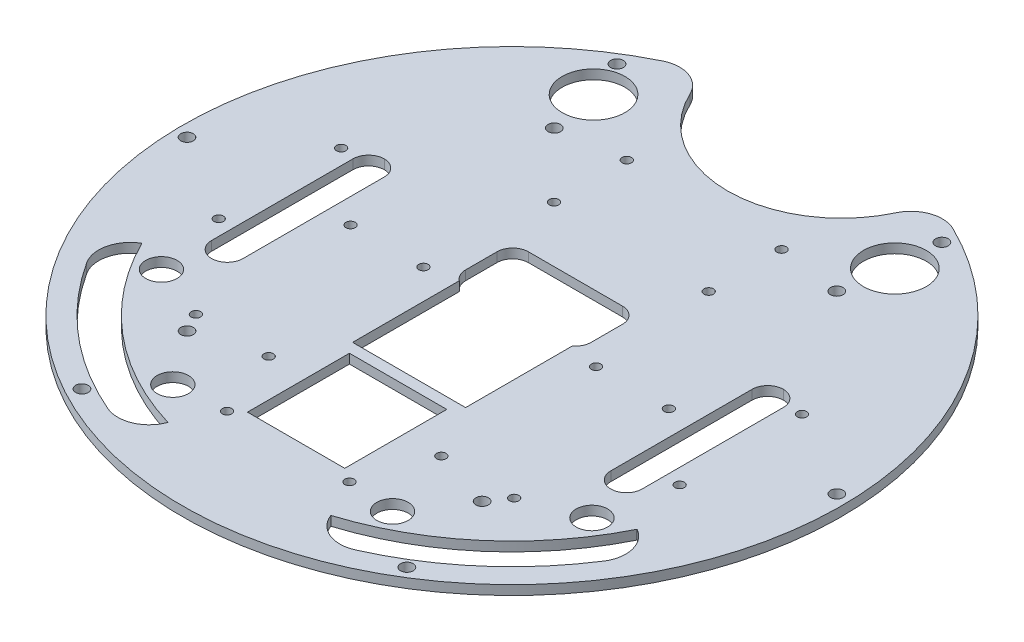
SolidWorks part; units mm, degrees
ref_plane "Alzado" through (0, 0, 0) normal (0, 0, 1) x (1, 0, 0)
ref_plane "Planta" through (0, 0, 0) normal (0, 1, 0) x (1, 0, 0)
ref_plane "Vista lateral" through (0, 0, 0) normal (1, 0, 0) x (0, 0, -1)
sketch "Croquis1" plane through (0, 0, 0) normal (0, 1, 0) x (1, 0, 0)
  circle A0 centre (0, 0) radius 105
  dimension "D1" = 210
extrude "Saliente-Extruir1" add sketch "Croquis1" along normal blind 3
sketch "Croquis2" plane through (0, 3, 0) normal (0, 1, 0) x (1, 0, 0)
  line L0 (-35.7167, 98.7386) -> (35.7167, 98.7386) construction
  line L1 (-29.7198, 68.7386) -> (25.5389, 68.7386) construction
  arc A0 (35.7167, 98.7386) -> (-35.7167, 98.7386) centre (0, 105) cw
  circle A2 centre (0, 0) radius 105 construction
  arc A3 (-35.7167, 98.7386) -> (35.7167, 98.7386) centre (0, 0) cw
  dimension "D1" = 30
extrude "Cortar-Extruir1" cut sketch "Croquis2" against normal up to surface (3 mm away) up to face at (0, 0, 105)
fillet "Redondeo1" radius 10 2 edges at (35.7167, 1.5, -98.7386) (-35.7167, 1.5, -98.7386)
sketch "Croquis3" plane through (0, 3, 0) normal (0, 1, 0) x (1, 0, 0)
  line L0 (0, 0) -> (0, -105) construction
  line L1 (-20, -105) -> (-20, -82) construction
  line L2 (-20, -82) -> (20, -82) construction
  line L3 (20, -82) -> (20, -105) construction
  line L4 (20, -105) -> (-20, -105) construction
  line L5 (-61.0141, 58.3205) -> (-85.2628, 72.3205)
  line L6 (-20, -82) -> (20, -82)
  line L7 (-20, -82) -> (-20, -110)
  line L8 (-20, -110) -> (20, -110)
  line L9 (20, -82) -> (20, -110)
  line L10 (-61.0141, 58.3205) -> (-81.0141, 23.6795)
  line L11 (-81.0141, 23.6795) -> (-105.2628, 37.6795)
  line L12 (-85.2628, 72.3205) -> (-105.2628, 37.6795)
  line L13 (81.0141, 23.6795) -> (105.2628, 37.6795)
  line L14 (81.0141, 23.6795) -> (61.0141, 58.3205)
  line L15 (61.0141, 58.3205) -> (85.2628, 72.3205)
  line L16 (105.2628, 37.6795) -> (85.2628, 72.3205)
  arc A0 (-46.2555, 94.2626) -> (46.2555, 94.2626) centre (0, 0) ccw construction
  point P23 (0, 0)
  point P29 (0, 0)
  point P44 (0, 0)
  dimension "D5" = 3
  dimension "D7" = 110
  dimension "D1" = 20
  dimension "D2" = 40
  dimension "D3" = 23
  dimension "D4" = 105
sketch "Croquis6" plane through (0, 3, 0) normal (0, 1, 0) x (1, 0, 0)
  line L0 (-14.5, -50) -> (-27.5, -50) construction
  line L1 (15.5, -50) -> (27.5, -50) construction
  line L2 (-27.5, -50) -> (-27.5, -0.7) construction
  line L3 (-27.5, -0.7) -> (-50.7, -0.7) construction
  line L4 (-27.5, -50) -> (-50.7, -50) construction
  line L5 (27.5, -50) -> (50.7, -50) construction
  line L6 (27.5, -50) -> (27.5, -0.7) construction
  line L7 (27.5, -0.7) -> (50.7, -0.7) construction
  line L8 (-24.6, 38) -> (24.7, 38) construction
  line L11 (-24.6, 38) -> (-24.6, 61.2) construction
  line L13 (24.7, 38) -> (24.7, 61.2) construction
  circle A0 centre (-50.7, -50) radius 1.5
  circle A1 centre (-27.5, -50) radius 1.5
  circle A2 centre (-50.7, -0.7) radius 1.5
  circle A3 centre (-27.5, -0.7) radius 1.5
  circle A4 centre (50.7, -0.7) radius 1.5
  circle A5 centre (50.7, -50) radius 1.5
  circle A6 centre (27.5, -50) radius 1.5
  circle A7 centre (27.5, -0.7) radius 1.5
  circle A8 centre (-24.6, 38) radius 1.5
  circle A9 centre (-24.6, 61.2) radius 1.5
  circle A10 centre (24.7, 38) radius 1.5
  circle A11 centre (24.7, 61.2) radius 1.5
  arc A12 (-46.2555, 94.2626) -> (46.2555, 94.2626) centre (0, 0) ccw construction
  arc A13 (-32.8037, 89.5468) -> (32.8037, 89.5468) centre (0, 105) ccw construction
  dimension "D1" = 3
  dimension "D2" = 3
  dimension "D3" = 3
  dimension "D4" = 3
  dimension "D5" = 3
  dimension "D6" = 3
  dimension "D7" = 3
  dimension "D8" = 3
  dimension "D9" = 3
  dimension "D10" = 3
  dimension "D11" = 3
  dimension "D12" = 3
  dimension "D17" = 23.2
  dimension "D18" = 23.2
  dimension "D19" = 23.2
  dimension "D20" = 23.2
  dimension "D23" = 23.2
  dimension "D24" = 23.2
  dimension "D13" = 27.5
  dimension "D14" = 27.5
  dimension "D15" = 49.3
  dimension "D16" = 49.3
  dimension "D21" = 67
  dimension "D22" = 49.3
  dimension "D25" = 24.6
  dimension "D26" = 50
  dimension "D27" = 50
extrude "Cortar-Extruir10" cut sketch "Croquis6" against normal through all
sketch "Croquis12" plane through (0, 3, 0) normal (0, 1, 0) x (1, 0, 0)
  line L0 (0, -110) -> (0, -89) construction
  line L1 (-19, -83.92) -> (-19, -103.2666) construction
  line L2 (-19, -83.92) -> (19, -83.92) construction
  line L3 (-19, -103.2666) -> (19, -103.2666) construction
  line L4 (-19, -49.2666) -> (-11.5, -49.2666) construction
  line L5 (-17, -17.8467) -> (-17, -34.8467) construction
  line L6 (19, -103.2666) -> (19, -83.92) construction
  line L7 (-19, -49.2666) -> (-19, -83.92) construction
  line L8 (-15.5, -36.2666) -> (15.5, -36.2666)
  line L9 (-15.5, -36.2666) -> (-15.5, -68.7666)
  line L10 (-15.5, -68.7666) -> (15.5, -68.7666)
  line L11 (15.5, -36.2666) -> (15.5, -68.7666)
  line L12 (0, 115.6879) -> (0, -186.0714) construction
  line L13 (-18, -32.7666) -> (18, -32.7666)
  line L14 (-18, -32.7666) -> (-18, -9.7666)
  line L15 (-18, -9.7666) -> (18, -9.7666)
  line L16 (18, -32.7666) -> (18, -9.7666)
  line L20 (-116.0467, -20.7666) -> (168.8024, -20.7666) construction
  line L24 (-17, -14.8467) -> (-17, -37.8467) construction
  arc A0 (-46.2555, 94.2626) -> (46.2555, 94.2626) centre (0, 0) ccw construction
  dimension "D6" = 15.1533
  dimension "D7" = 15.5
  dimension "D8" = 11
  dimension "D1" = 21
  dimension "D2" = 38
  dimension "D3" = 19.3467
  dimension "D4" = 7.5
  dimension "D5" = 13
  dimension "D16" = 31
  dimension "D17" = 32.5
  dimension "D19" = 3.5
  dimension "D20" = 23
  dimension "D21" = 36
  dimension "D22" = 18
extrude "Cortar-Extruir13" cut sketch "Croquis12" against normal through all
sketch "Croquis16" plane through (0, 3, 0) normal (0, 1, 0) x (1, 0, 0)
  line L0 (-22, -82) -> (22, -82) construction
  line L1 (0, -113.1983) -> (0, -59.2856) construction
  line L2 (-22, -82) -> (-22, -68.7666) construction
  line L3 (-22, -68.7666) -> (22, -68.7666) construction
  line L4 (22, -68.7666) -> (22, -82) construction
  line L5 (-134.3371, 0) -> (162.6467, 0) construction
  line L6 (-70.4267, 22) -> (-70.4267, -22) construction
  line L7 (-70.4267, 22) -> (-102.6694, 22) construction
  line L8 (-102.6694, 22) -> (-102.6694, -22) construction
  line L9 (-102.6694, -22) -> (-70.4267, -22) construction
  line L10 (-20, -82) -> (20, -82) construction
  circle A0 centre (-19, -71.7666) radius 1.5
  circle A1 centre (20, -71.7666) radius 1.5
  arc A2 (-46.2555, 94.2626) -> (46.2555, 94.2626) centre (0, 0) ccw construction
  circle A3 centre (-73.4267, 19) radius 1.5
  circle A4 centre (-73.4267, -20) radius 1.5
  circle A5 centre (73.4267, 19) radius 1.5
  circle A6 centre (73.4267, -20) radius 1.5
  dimension "D3" = 3
  dimension "D4" = 3
  dimension "D5" = 3
  dimension "D6" = 3
  dimension "D7" = 3
  dimension "D8" = 2
  dimension "D12" = 3
  dimension "D13" = 3
  dimension "D14" = 3
  dimension "D15" = 3
  dimension "D16" = 3
  dimension "D17" = 2
  dimension "D1" = 44
  dimension "D2" = 22
  dimension "D9" = 44
  dimension "D10" = 22
  dimension "D11" = 32.2427
extrude "Cortar-Extruir16" cut sketch "Croquis16" against normal through all
sketch "Croquis17" plane through (0, 3, 0) normal (0, 1, 0) x (1, 0, 0)
  line L0 (0, -118.708) -> (0, 122.5947) construction
  line L1 (-174.3343, -39) -> (185.7554, -39) construction
  line L2 (-20, -108.1665) -> (-20, -82) construction
  line L3 (20, -108.1665) -> (20, -82) construction
  line L4 (-31.4253, -100.1871) -> (-20.4928, -71.6203) construction
  line L5 (21.4314, -71.3181) -> (32.3639, -99.8878) construction
  line L6 (-20, -82) -> (-20, -110) construction
  line L7 (20, -82) -> (20, -110) construction
  arc A1 (-78.886, -39) -> (-25.3354, -84.2741) centre (0, 0) ccw
  arc A2 (-32.8037, 89.5468) -> (32.8037, 89.5468) centre (0, 105) ccw construction
  arc A4 (26.2784, -83.9848) -> (78.886, -39) centre (0, 0) ccw
  arc A5 (-46.2555, 94.2626) -> (46.2555, 94.2626) centre (0, 0) ccw construction
  circle A6 centre (-19, -71.7666) radius 1.5 construction
  circle A7 centre (20, -71.7666) radius 1.5 construction
  arc A8 (-46.2555, 94.2626) -> (46.2555, 94.2626) centre (0, 0) ccw construction
  dimension "D6" = 88
  dimension "D1" = 144
  dimension "D2" = 30.5873
  dimension "D3" = 20.942
  dimension "D4" = 30.59
  dimension "D5" = 20.94
extrude "Cortar-Extruir-Lámina2" cut sketch "Croquis17" against normal blind 10 thin thin type one direction wall 10
sketch "Croquis18" plane through (0, 3, 0) normal (0, 1, 0) x (1, 0, 0)
  line L1 (0, -111.168) -> (0, 0) construction
  line L2 (0, 0) -> (0, 105) construction
  line L3 (-20, 20.2334) -> (20, 20.2334)
  line L4 (-20, 20.2334) -> (-20, 0.2334)
  line L5 (-20, 0.2334) -> (20, 0.2334)
  line L6 (20, 20.2334) -> (20, 0.2334)
  line L7 (18, -9.7666) -> (-18, -9.7666) construction
  line L8 (-63.5839, -43.0959) -> (-63.5839, 83.5589) construction
  line L9 (-68.5839, 22.9041) -> (-58.5839, 22.9041)
  line L10 (-68.5839, 22.9041) -> (-68.5839, -32.0959)
  line L11 (-68.5839, -32.0959) -> (-58.5839, -32.0959)
  line L12 (-58.5839, 22.9041) -> (-58.5839, -32.0959)
  line L13 (68.5839, 22.9041) -> (58.5839, 22.9041)
  line L14 (68.5839, -32.0959) -> (58.5839, -32.0959)
  line L15 (58.5839, 22.9041) -> (58.5839, -32.0959)
  line L16 (68.5839, 22.9041) -> (68.5839, -32.0959)
  line L17 (-20, -82) -> (-20, -110) construction
  circle A0 centre (-35, -73.0479) radius 5
  circle A1 centre (-68.5839, -43.0959) radius 5
  arc A2 (-78.886, -39) -> (-25.3354, -84.2741) centre (0, 0) ccw construction
  circle A3 centre (35, -73.0479) radius 5
  circle A4 centre (68.5839, -43.0959) radius 5
  circle A5 centre (-48, 74) radius 10
  circle A6 centre (48, 74) radius 10
  arc A7 (-32.8037, 89.5468) -> (32.8037, 89.5468) centre (0, 105) ccw construction
  arc A9 (-46.2555, 94.2626) -> (46.2555, 94.2626) centre (0, 0) ccw construction
  arc A10 (-46.2555, 94.2626) -> (46.2555, 94.2626) centre (0, 0) ccw construction
  dimension "D1" = 10
  dimension "D2" = 10
  dimension "D3" = 81
  dimension "D4" = 81
  dimension "D5" = 45
  dimension "D6" = 15
  dimension "D7" = 20
  dimension "D8" = 20
  dimension "D9" = 48
  dimension "D10" = 48
  dimension "D11" = 74
  dimension "D12" = 74
  dimension "D13" = 40
  dimension "D14" = 20
  dimension "D15" = 20
  dimension "D16" = 30
  dimension "D17" = 55
  dimension "D18" = 10
  dimension "D19" = 5
  dimension "D20" = 11
extrude "Cortar-Extruir17" cut sketch "Croquis18" against normal through all
fillet "Redondeo2" radius 5 12 edges at (20, 1.5, -0.2334) (20, 1.5, -20.2334) (-20, 1.5, -0.2334) (-20, 1.5, -20.2334) (68.5839, 1.5, 32.0959) (58.5839, 1.5, 32.0959) (68.5839, 1.5, -22.9041) (58.5839, 1.5, -22.9041) (-58.5839, 1.5, 32.0959) (-68.5839, 1.5, 32.0959) (-58.5839, 1.5, -22.9041) (-68.5839, 1.5, -22.9041)
fillet "Redondeo3" radius 10 4 edges at (87.8503, 1.5, 43.4318) (29.2646, 1.5, 93.5285) (-28.2145, 1.5, 93.8507) (-87.8503, 1.5, 43.4318)
sketch "Croquis19" plane through (0, 3, 0) normal (0, 1, 0) x (1, 0, 0)
  circle A0 centre (-100.9677, -2.5529) radius 2
  arc A1 (-46.2555, 94.2626) -> (46.2555, 94.2626) centre (0, 0) ccw construction
  circle A2 centre (-52.6947, 86.1642) radius 2
  circle A3 centre (48.273, 88.7171) radius 2
  circle A4 centre (100.9677, 2.5529) radius 2
  circle A5 centre (52.6947, -86.1642) radius 2
  circle A6 centre (-48.273, -88.7171) radius 2
  arc A7 (-32.8037, 89.5468) -> (32.8037, 89.5468) centre (0, 105) ccw construction
  point P5 (0, 68.7386)
  point P18 (0, 0)
  point P19 (0, 0)
  dimension "D1" = 4
  dimension "D2" = 101
  dimension "D3" = 123.6
  dimension "D4" = 6
extrude "Cortar-Extruir18" cut sketch "Croquis19" against normal through all
sketch "Croquis20" plane through (0, 3, 0) normal (0, 1, 0) x (1, 0, 0)
  line L1 (-15.5, -36.2666) -> (-15.5, -68.7666) construction
  line L2 (0, -119.667) -> (0, 0) construction
  line L4 (15.5, -68.7666) -> (15.5, -36.2666) construction
  line L5 (45, 58.5) -> (-45, 58.5) construction
  circle A0 centre (-47.5, -56) radius 2
  circle A1 centre (-50.7, -50) radius 1.5 construction
  circle A3 centre (48, 74) radius 10 construction
  circle A5 centre (46.5, -56) radius 2
  circle A6 centre (50.7, -50) radius 1.5 construction
  circle A7 centre (45, 58.5) radius 2
  circle A8 centre (24.7, 38) radius 1.5 construction
  circle A10 centre (-45, 58.5) radius 2
  dimension "D1" = 4
  dimension "D2" = 6
  dimension "D3" = 32
  dimension "D4" = 31
  dimension "D5" = 6
  dimension "D6" = 4
  dimension "D7" = 4
  dimension "D8" = 20.3
  dimension "D9" = 15.5
  dimension "D11" = 4
  dimension "D10" = 90
extrude "Cortar-Extruir19" cut sketch "Croquis20" against normal through all
sketch "Croquis21" plane through (0, 3, 0) normal (0, 1, 0) x (1, 0, 0)
  line L1 (-18, -9.7666) -> (18, -9.7666)
  line L2 (-18, -9.7666) -> (-18, 2.2334)
  line L3 (-18, 2.2334) -> (18, 2.2334)
  line L4 (18, -9.7666) -> (18, 2.2334)
  dimension "D1" = 36
  dimension "D2" = 12
extrude "Cortar-Extruir20" cut sketch "Croquis21" against normal through all
